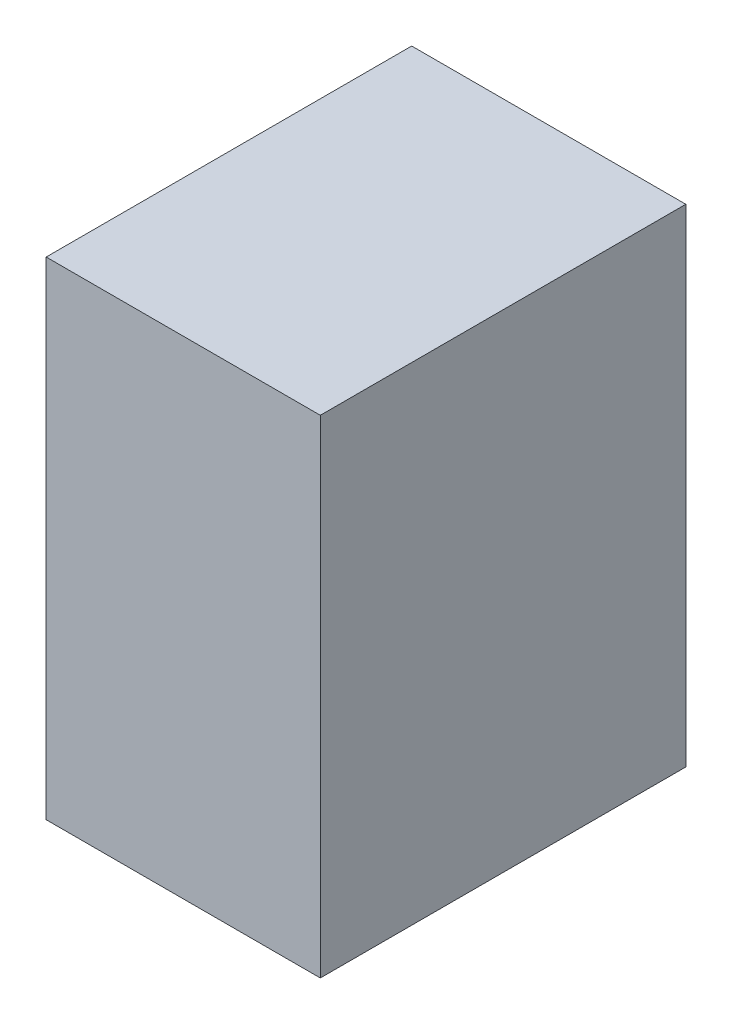
SolidWorks part; units mm, degrees
ref_plane "Спереди" through (0, 0, 0) normal (0, 0, 1) x (1, 0, 0)
ref_plane "Сверху" through (0, 0, 0) normal (0, 1, 0) x (1, 0, 0)
ref_plane "Справа" through (0, 0, 0) normal (1, 0, 0) x (0, 0, -1)
sketch "Эскиз1" plane through (0, 0, 0) normal (0, 1, 0) x (1, 0, 0)
  line L1 (0, 0) -> (450, 0)
  line L2 (0, 0) -> (0, 600)
  line L3 (0, 600) -> (450, 600)
  line L4 (450, 0) -> (450, 600)
  point P4 (0, 0)
extrude "Бобышка-Вытянуть1" add sketch "Эскиз1" along normal blind 800
